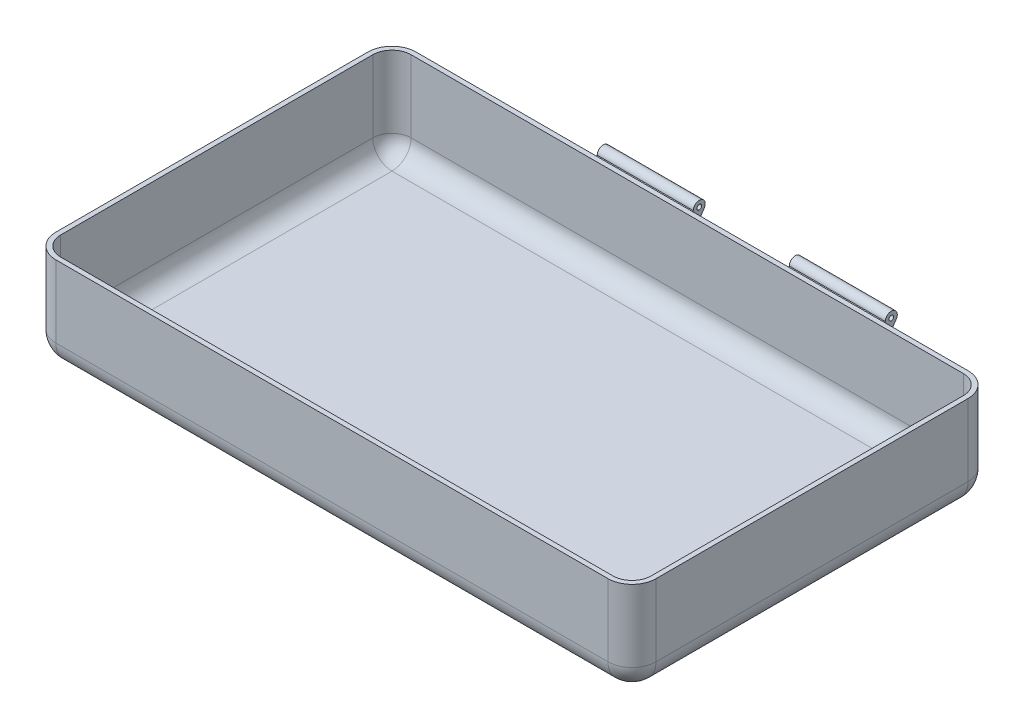
SolidWorks part; units mm, degrees
ref_plane "Alzado" through (0, 0, 0) normal (0, 0, 1) x (1, 0, 0)
ref_plane "Planta" through (0, 0, 0) normal (0, 1, 0) x (1, 0, 0)
ref_plane "Vista lateral" through (0, 0, 0) normal (1, 0, 0) x (0, 0, -1)
sketch "Croquis1" plane through (0, 0, 0) normal (0, 1, 0) x (1, 0, 0)
  line L1 (-125, -75) -> (125, -75)
  line L2 (-125, -75) -> (-125, 75)
  line L3 (-125, 75) -> (125, 75)
  line L4 (125, -75) -> (125, 75)
  line L5 (-125, -75) -> (125, 75) construction
  line L6 (-125, 75) -> (125, -75) construction
  point P0 (0, 0)
  dimension "D1" = 250
  dimension "D2" = 150
extrude "Saliente-Extruir1" add sketch "Croquis1" along normal mid plane 40 contours L2 L3 L4 L1
fillet "Redondeo1" radius 10 8 edges at (0, -20, -75) (-125, 0, -75) (125, 0, -75) (-125, 0, 75) (-125, -20, 0) (125, -20, 0) (125, 0, 75) (0, -20, 75)
shell "Vaciado2" thickness 2 removed face at (0, 20, 0)
sketch "Croquis2" plane through (0, 0, 0) normal (1, 0, 0) x (0, 0, -1)
  line L0 (75, 20) -> (65, 20) construction
  line L1 (80.0795, 18.6124) -> (75, 11)
  line L2 (75, 20) -> (75, -10) construction
  line L3 (75, 19) -> (75.5, 20)
  line L4 (75, 19) -> (75, 11)
  circle A0 centre (78, 20) radius 1
  circle A1 centre (78, 20) radius 2.5
  dimension "D1" = 2
  dimension "D5" = 1.5
  dimension "D2" = 1
  dimension "D3" = 8
  dimension "D4" = 3
extrude "Saliente-Extruir2" add sketch "Croquis2" along normal blind 40 from offset 40 contours A1 L3 L4 L1 | A1 A0 region at (0, 15.782, -76.3896) region at (0, 17.6751, -77.2955)
extrude "Saliente-Extruir3" add sketch "Croquis2<3>" against normal blind 40 contours A1 L3 L4 L1 | A1 A0 region at (0, 15.782, -76.3896) region at (0, 17.6751, -77.2955)
sketch "Croquis2<3>" plane through (0, 0, 0) normal (1, 0, 0) x (0, 0, -1) same geometry as "Croquis2"
